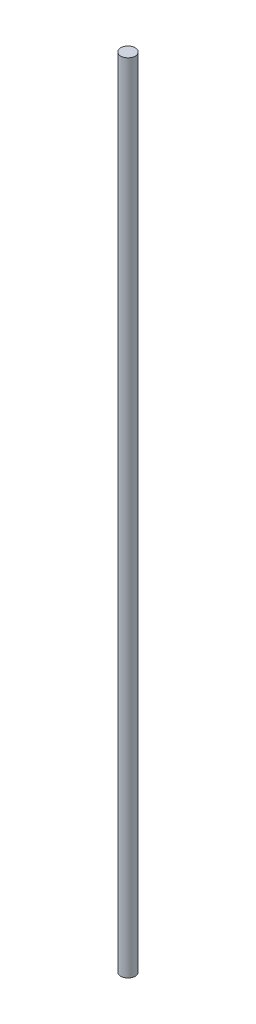
SolidWorks part; units mm, degrees
material "AISI Type A2 Tool Steel"
ref_plane "Front Plane" through (0, 0, 0) normal (0, 0, 1) x (1, 0, 0)
ref_plane "Top Plane" through (0, 0, 0) normal (0, 1, 0) x (1, 0, 0)
ref_plane "Right Plane" through (0, 0, 0) normal (1, 0, 0) x (0, 0, -1)
sketch "Sketch1" plane through (0, 0, 0) normal (0, 1, 0) x (1, 0, 0)
  circle A0 centre (0, 0) radius 1.5
  dimension "D1" = 3
extrude "Boss-Extrude1" add sketch "Sketch1" along normal blind 165
